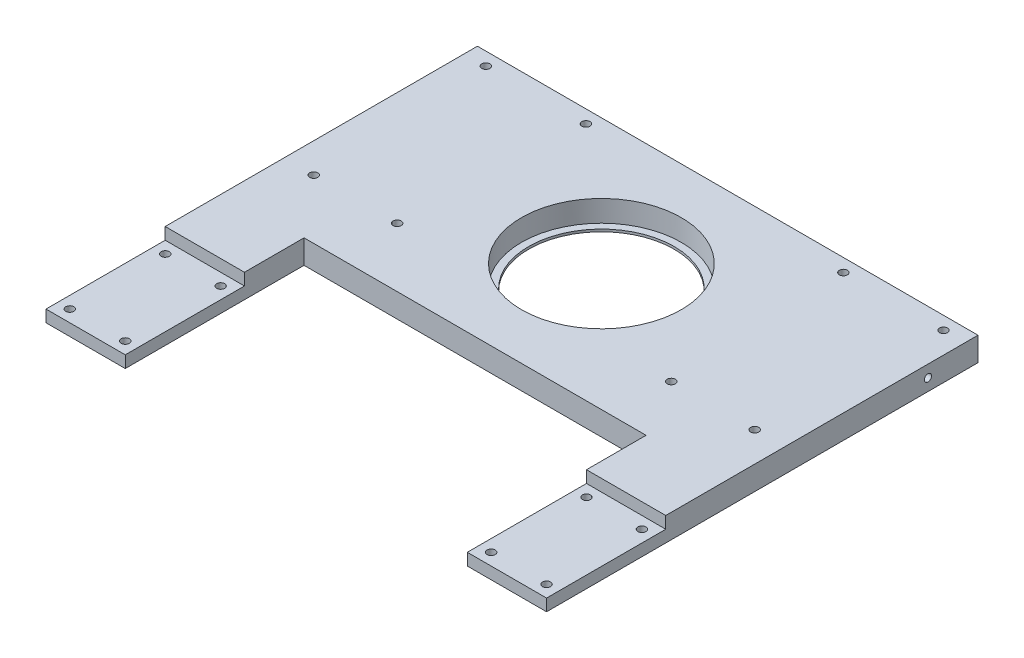
SolidWorks part; units mm, degrees
ref_plane "Ebene vorne" through (0, 0, 0) normal (0, 0, 1) x (1, 0, 0)
ref_plane "Ebene oben" through (0, 0, 0) normal (0, 1, 0) x (1, 0, 0)
ref_plane "Ebene rechts" through (0, 0, 0) normal (1, 0, 0) x (0, 0, -1)
sketch "Skizze1" plane through (0, 0, 0) normal (0, 1, 0) x (1, 0, 0)
  line L1 (-105, -210) -> (105, -210)
  line L2 (-105, -210) -> (-105, 210)
  line L3 (-105, 210) -> (105, 210)
  line L4 (105, -210) -> (105, 210)
  line L5 (-105, -210) -> (105, 210) construction
  line L6 (-105, 210) -> (105, -210) construction
  point P0 (0, 0)
  dimension "D1" = 210
  dimension "D2" = 420
extrude "Aufsatz-Linear austragen1" add sketch "Skizze1" along normal blind 10
ref_plane "Ebene1" through (0, -97.5366, 81.8429) normal (0, -0.766, 0.6428) x (1, 0, 0)
sketch "Skizze2" plane through (0, -97.5366, 81.8429) normal (0, -0.766, 0.6428) x (1, 0, 0)
  line L1 (-105, 167.2972) -> (105, 167.2972) construction
  circle A0 centre (0, 147.2972) radius 5
  dimension "D1" = 10
  dimension "D2" = 20
extrude "Schnitt-Linear austragen1" [suppressed] cut sketch "Skizze2" against normal blind 30 and the other way blind 10
sketch "Skizze3" [suppressed] plane through (0, -67.9923, 57.0523) normal (0, -0.766, 0.6428) x (1, 0, 0)
  circle A0 centre (0, 101.3345) radius 5
  dimension "D1" = 10
extrude "Aufsatz-Linear austragen2" [suppressed] add sketch "Skizze3" along normal blind 0.1
sketch "Skizze4" plane through (0, -97.5366, 81.8429) normal (0, -0.766, 0.6428) x (1, 0, 0)
  line L0 (0, 167.2972) -> (0, 159.9002) construction
  line L1 (-105, 167.2972) -> (105, 167.2972) construction
  line L2 (-25, 167.2972) -> (-25, 202.2972)
  line L3 (-25, 202.2972) -> (25, 202.2972)
  line L4 (-25, 167.2972) -> (25, 167.2972)
  line L5 (25, 167.2972) -> (25, 202.2972)
  point P10 (0, 202.2972)
  dimension "D1" = 50
  dimension "D2" = 35
extrude "Aufsatz-Linear austragen3" [suppressed] add sketch "Skizze4" against normal blind 10 separate body
sketch "Skizze5" plane through (0, 10, 0) normal (0, 1, 0) x (1, 0, 0)
  line L0 (0, 0) -> (0, -210) construction
  line L1 (-105, -210) -> (105, -210) construction
  line L2 (105, -210) -> (18, -210)
  line L3 (-18, -210) -> (-105, -56)
  line L4 (-105, 210) -> (-105, -210) construction
  line L5 (-105, -56) -> (-105, -210)
  line L6 (-105, -210) -> (-18, -210)
  line L7 (105, -56) -> (105, -210)
  line L8 (18, -210) -> (105, -56)
  line L9 (-105, 210) -> (-105, 125)
  line L10 (-105, 125) -> (105, 125)
  line L11 (105, -210) -> (105, 210) construction
  line L12 (105, 125) -> (105, 210)
  line L13 (105, 210) -> (-105, 210)
  line L14 (71.7468, -56) -> (-71.7468, -56)
  line L15 (-71.7468, -56) -> (-2.8247, -178)
  line L16 (71.7468, -56) -> (2.8247, -178)
  line L17 (-2.8247, -178) -> (2.8247, -178)
  line L18 (2.8247, -178) -> (0, -183) construction
  line L19 (-2.8247, -178) -> (0, -183) construction
  point P27 (0, -56)
  dimension "D1" = 36
  dimension "D2" = 154
  dimension "D3" = 85
  dimension "D4" = 32
  dimension "D5" = 27
extrude "Schnitt-Linear austragen2" cut sketch "Skizze5" against normal blind 10
sketch "Skizze6" plane through (0, 10, 0) normal (0, 1, 0) x (1, 0, 0)
  line L0 (0, -210) -> (0, -178) construction
  line L1 (-18, -210) -> (18, -210) construction
  line L2 (-2.8247, -178) -> (2.8247, -178) construction
  line L3 (0, -196.59) -> (-21.075, -196.59) construction
  circle A0 centre (-11, -205) radius 1.7
  circle A1 centre (-11, -188.18) radius 1.7
  circle A2 centre (11, -205) radius 1.7
  circle A3 centre (11, -188.18) radius 1.7
  dimension "D1" = 3.4
  dimension "D2" = 11
  dimension "D3" = 5
  dimension "D4" = 13.41
extrude "Schnitt-Linear austragen3" cut sketch "Skizze6" against normal through all
sketch "Skizze7" plane through (0, 0, 0) normal (0, -1, 0) x (1, 0, 0)
  line L0 (-11, 205) -> (-11, 210) construction
  line L1 (-18, 210) -> (18, 210) construction
  line L2 (-11, 205) -> (-5.1092, 205) construction
  line L3 (-11, 208.4064) -> (-8.05, 206.7032)
  line L4 (-8.05, 206.7032) -> (-8.05, 203.2968)
  line L5 (-11, 201.5936) -> (-8.05, 203.2968)
  line L6 (-11, 201.5936) -> (-13.95, 203.2968)
  line L7 (-13.95, 206.7032) -> (-13.95, 203.2968)
  line L8 (-11, 208.4064) -> (-13.95, 206.7032)
  line L9 (0, 210) -> (0, 121.6034) construction
  line L10 (11, 205) -> (11, 188.18) construction
  line L11 (11, 196.59) -> (0, 196.59) construction
  line L12 (11, 208.4064) -> (8.05, 206.7032)
  line L13 (11, 201.5936) -> (8.05, 203.2968)
  line L14 (8.05, 206.7032) -> (8.05, 203.2968)
  line L15 (11, 201.5936) -> (13.95, 203.2968)
  line L16 (13.95, 206.7032) -> (13.95, 203.2968)
  line L17 (11, 208.4064) -> (13.95, 206.7032)
  line L18 (-8.05, 186.4768) -> (-8.05, 189.8832)
  line L19 (-11, 191.5864) -> (-13.95, 189.8832)
  line L20 (-11, 191.5864) -> (-8.05, 189.8832)
  line L21 (-13.95, 186.4768) -> (-13.95, 189.8832)
  line L22 (-11, 184.7736) -> (-13.95, 186.4768)
  line L23 (-11, 184.7736) -> (-8.05, 186.4768)
  line L24 (8.05, 186.4768) -> (8.05, 189.8832)
  line L25 (11, 191.5864) -> (8.05, 189.8832)
  line L26 (11, 191.5864) -> (13.95, 189.8832)
  line L27 (13.95, 186.4768) -> (13.95, 189.8832)
  line L28 (11, 184.7736) -> (13.95, 186.4768)
  line L29 (11, 184.7736) -> (8.05, 186.4768)
  point P10 (-8.05, 205)
  dimension "D1" = 120
  dimension "D2" = 5.9
extrude "Schnitt-Linear austragen4" cut sketch "Skizze7" against normal blind 4
sketch "Skizze8" plane through (0, 10, 0) normal (0, 1, 0) x (1, 0, 0)
  line L0 (105, 115.41) -> (78.872, 115.41) construction
  line L1 (105, -56) -> (105, 125) construction
  line L2 (-105, 125) -> (105, 125) construction
  dimension "D1" = 9.59
ref_plane "Ebene2" through (0, 62.6966, -52.6087) normal (0, 0.766, -0.6428) x (-1, 0, 0)
sketch "Skizze9" plane through (0, 62.6966, -52.6087) normal (0, 0.766, -0.6428) x (-1, 0, 0)
  line L0 (-105, -81.9813) -> (-78.872, -81.9813) construction
  line L1 (-105, 49.3264) -> (-105, -89.3277) construction
  line L2 (0, -45.2589) -> (0, -16.2619) construction
  circle A0 centre (-100, -81.9813) radius 1.7
  circle A1 centre (100, -81.9813) radius 1.7
  circle A2 centre (-30, -81.9813) radius 1.7
  circle A3 centre (30, -81.9813) radius 1.7
  dimension "D1" = 3.4
  dimension "D2" = 5
  dimension "D3" = 30
extrude "Schnitt-Linear austragen5" [suppressed] cut sketch "Skizze9" against normal through all and the other way through all
ref_plane "Ebene3" through (0, 55.0361, -46.1808) normal (0, 0.766, -0.6428) x (-1, 0, 0)
sketch "Skizze10" [suppressed] plane through (0, 55.0361, -46.1808) normal (0, 0.766, -0.6428) x (-1, 0, 0)
  line L0 (-95, -81.9813) -> (-100, -81.9813) construction
  line L1 (-95, -81.9813) -> (-95, -30.0694) construction
  line L2 (-95, -78.7482) -> (-97.8, -80.3647)
  line L3 (-97.8, -80.3647) -> (-97.8, -83.5979)
  line L4 (-95, -85.2145) -> (-97.8, -83.5979)
  line L5 (-95, -85.2145) -> (-92.2, -83.5979)
  line L6 (-92.2, -80.3647) -> (-92.2, -83.5979)
  line L7 (-95, -78.7482) -> (-92.2, -80.3647)
  line L8 (0, 0) -> (0, -45.6283) construction
  line L9 (-30, -81.9813) -> (-95, -81.9813) construction
  line L10 (-62.5, -81.9813) -> (-62.5, -23.1343) construction
  line L11 (-32.8, -80.3647) -> (-32.8, -83.5979)
  line L12 (-30, -85.2145) -> (-32.8, -83.5979)
  line L13 (-30, -85.2145) -> (-27.2, -83.5979)
  line L14 (-27.2, -80.3647) -> (-27.2, -83.5979)
  line L15 (-30, -78.7482) -> (-27.2, -80.3647)
  line L16 (-30, -78.7482) -> (-32.8, -80.3647)
  line L17 (95, -78.7482) -> (92.2, -80.3647)
  line L18 (92.2, -80.3647) -> (92.2, -83.5979)
  line L19 (95, -85.2145) -> (92.2, -83.5979)
  line L20 (95, -85.2145) -> (97.8, -83.5979)
  line L21 (97.8, -80.3647) -> (97.8, -83.5979)
  line L22 (95, -78.7482) -> (97.8, -80.3647)
  line L23 (30, -78.7482) -> (32.8, -80.3647)
  line L24 (30, -78.7482) -> (27.2, -80.3647)
  line L25 (27.2, -80.3647) -> (27.2, -83.5979)
  line L26 (30, -85.2145) -> (27.2, -83.5979)
  line L27 (30, -85.2145) -> (32.8, -83.5979)
  line L28 (32.8, -80.3647) -> (32.8, -83.5979)
  point P9 (-97.8, -81.9813)
  point P31 (97.8, -81.9813)
  dimension "D1" = 120
  dimension "D2" = 5.6
extrude "Schnitt-Linear austragen6" [suppressed] cut sketch "Skizze10" against normal blind 10 and the other way blind 5
sketch "Skizze13" plane through (0, 10, 0) normal (0, 1, 0) x (1, 0, 0)
  line L0 (71.7468, -56) -> (105, -56) construction
  line L1 (71.7468, -56) -> (96.9548, -70.2409) construction
  line L2 (105, -56) -> (18, -210) construction
  line L3 (0, 0) -> (0, -38.1435) construction
  line L4 (2.8247, -178) -> (71.7468, -56) construction
  line L5 (84.3508, -63.1205) -> (108.762, -19.9098) construction
  line L6 (105, -56) -> (105, 125) construction
  line L7 (88.3734, -56) -> (88.3734, -1) construction
  line L8 (99, -58.9512) -> (105.7595, -46.9862) construction
  line L9 (87.7845, -86.4734) -> (62.5765, -72.2325) construction
  line L10 (77.1638, -80.4734) -> (91.1741, -80.4734) construction
  circle A0 centre (99, -58.9512) radius 1.7
  circle A1 centre (76.9708, -58.9512) radius 1.7
  circle A2 centre (86.8414, -80.4734) radius 1.7
  circle A3 centre (-86.8414, -80.4734) radius 1.7
  circle A4 centre (-99, -58.9512) radius 1.7
  circle A5 centre (-76.9708, -58.9512) radius 1.7
  dimension "D1" = 6
  dimension "D5" = 35
  dimension "D3" = 3.4
  dimension "D6" = 3.4
  dimension "D2" = 6
  dimension "D4" = 6
extrude "Schnitt-Linear austragen7" [suppressed] cut sketch "Skizze13" against normal through all
sketch "Skizze14" plane through (103.579, 0, 58.5154) normal (0.8707, 0, 0.4919) x (0.4919, 0, -0.8707)
  line L0 (-32.111, 5) -> (-32.111, 10)
  line L5 (2.889, 0) -> (2.889, 10) construction
  line L6 (-32.111, 5) -> (2.889, 5)
  line L7 (2.889, 10) -> (-173.9866, 10) construction
  line L8 (-32.111, 10) -> (2.889, 10)
  line L9 (2.889, 10) -> (2.889, 5)
  dimension "D1" = 35
extrude "Schnitt-Linear austragen8" [suppressed] cut sketch "Skizze14" against normal up to surface (28.9525 mm away)
mirror "Spiegeln1" [suppressed] about plane through (0, 0, 0) normal (1, 0, 0)
sketch "Skizze15" [suppressed] plane through (95, 0, 0) normal (1, 0, 0) x (0, 0, -1)
  line L0 (4, 10) -> (4, 0)
  line L1 (4, 0) -> (65, 0)
  line L2 (65, 0) -> (65, 10)
  line L3 (65, 10) -> (4, 10)
extrude "Schnitt-Linear austragen9" [suppressed] cut sketch "Skizze15" against normal through all
sketch "Skizze16" plane through (0, 0, 0) normal (0, -1, 0) x (1, 0, 0)
  line L0 (0, 210) -> (0, 178) construction
  line L1 (-18, 210) -> (18, 210) construction
  line L2 (-2.8247, 178) -> (2.8247, 178) construction
  line L3 (11, 196.59) -> (0, 196.59) construction
  line L4 (11, 205) -> (11, 188.18) construction
  line L6 (-17.5, 193.09) -> (17.5, 193.09)
  line L7 (-17.5, 193.09) -> (-17.5, 200.09)
  line L8 (-17.5, 200.09) -> (17.5, 200.09)
  line L9 (17.5, 193.09) -> (17.5, 200.09)
  line L10 (-17.5, 193.09) -> (17.5, 200.09) construction
  line L11 (-17.5, 200.09) -> (17.5, 193.09) construction
  dimension "D1" = 7
  dimension "D2" = 35
extrude "Schnitt-Linear austragen10" cut sketch "Skizze16" against normal blind 5
sketch "Skizze17" plane through (17.5, 0, 0) normal (-1, 0, 0) x (0, 0, 1)
  line L0 (196.59, 0) -> (196.59, 11.1261) construction
  line L1 (193.09, 0) -> (200.09, 0) construction
  line L2 (193.09, 5) -> (196.59, 8.5)
  line L3 (196.59, 8.5) -> (200.09, 5)
  line L4 (200.09, 5) -> (193.09, 5)
  dimension "D1" = 90
extrude "Schnitt-Linear austragen11" cut sketch "Skizze17" along normal up to surface (35 mm away) up to face at (-17.5, 2.5, 196.59)
sketch "Skizze18" [suppressed] plane through (0, 10, 0) normal (0, 1, 0) x (1, 0, 0)
  line L0 (0, -210) -> (0, 0) construction
  line L1 (-18, -210) -> (18, -210) construction
  line L2 (62.5765, -72.2325) -> (35.4483, -67.5372)
  line L3 (15.3378, -155.8503) -> (-22.1774, -134.6566)
  line L4 (2.8247, -178) -> (62.5765, -72.2325) construction
  line L5 (-15.3378, -155.8503) -> (22.1774, -134.6566)
  line L6 (58.6594, -79.166) -> (40.7308, -76.063)
  line L7 (0, -147.1854) -> (19.5429, -147.1854) construction
  line L8 (0, -95.4) -> (31.4297, -95.4) construction
  line L9 (11.6488, -162.3803) -> (0, -155.7995)
  line L10 (-71.7468, -56) -> (-2.8247, -178) construction
  line L11 (0, -95.4) -> (-37.5153, -116.5937) construction
  line L12 (-37.5153, -116.5937) -> (-39.2566, -117.5774) construction
  line L13 (-11.6488, -162.3803) -> (0, -155.7995)
  line L14 (-58.6594, -79.166) -> (-40.7308, -76.063)
  line L15 (-62.5765, -72.2325) -> (-35.4483, -67.5372)
  circle A0 centre (0, -95.4) radius 33.5
  arc A1 (7.4594, -151.3994) -> (7.4594, -142.9713) centre (9.84, -147.1854) cw
  arc A2 (-7.4594, -151.3994) -> (-7.4594, -142.9713) centre (-9.84, -147.1854) ccw
  circle A3 centre (0, -95.4) radius 45.0879
  point P17 (0, -147.1854)
  point P36 (5, -147.1854)
  point P40 (-5, -147.1854)
  line M16 (62.5765, -72.2325) -> (2.8247, -178)
  line M18 (-2.8247, -178) -> (-71.7468, -56)
  dimension "D2" = 67
  dimension "D5" = 2
  dimension "D4" = 10
  dimension "D1" = 114.6
  dimension "D3" = 7.5
  dimension "D6" = 7.5
extrude "Aufsatz-Linear austragen4" [suppressed] add sketch "Skizze18" against normal blind 10 contours A3 L15 L14 M18 | A3 A0 M16 M18 | A3 L6 L2 M16 | A2 L5 L3 | A3 L3 L5 | L3 A1 L5 | L13 L9 L3 L5 M18 M16
sketch "Skizze19" [suppressed] plane through (0, 0, 0) normal (0, -1, 0) x (1, 0, 0)
  circle A0 centre (0, 35.4) radius 31.5
  circle A1 centre (0, 35.4) radius 33.5
  circle A2 centre (0, 35.4) radius 33.5 construction
  dimension "D1" = 63
extrude "Aufsatz-Linear austragen5" [suppressed] add sketch "Skizze19" against normal blind 1
sketch "Skizze20" plane through (0, 10, 0) normal (0, 1, 0) x (1, 0, 0)
  line L0 (105, 119.52) -> (55.4083, 119.52) construction
  line L1 (105, -56) -> (105, 125) construction
  line L2 (-105, 125) -> (105, 125) construction
  line L3 (0, 125) -> (0, 96.9732) construction
  line L4 (105, 43.82) -> (35.5869, 43.82) construction
  circle A0 centre (96, 119.52) radius 1.7
  circle A1 centre (54, 119.52) radius 1.7
  circle A2 centre (-54, 119.52) radius 1.7
  circle A3 centre (-96, 119.52) radius 1.7
  circle A4 centre (92.5, 43.82) radius 1.7
  circle A5 centre (57.5, 43.82) radius 1.7
  circle A6 centre (-92.5, 43.82) radius 1.7
  circle A7 centre (-57.5, 43.82) radius 1.7
  dimension "D1" = 3.4
  dimension "D2" = 5.48
  dimension "D3" = 9
  dimension "D4" = 42
  dimension "D5" = 75.7
  dimension "D6" = 12.5
  dimension "D7" = 35
extrude "Schnitt-Linear austragen12" cut sketch "Skizze20" against normal through all
sketch "Skizze21" plane through (0, 10, 0) normal (0, 1, 0) x (1, 0, 0)
  line L0 (-71.7468, -56) -> (-71.7468, 19)
  line L1 (-71.7468, 19) -> (71.7468, 19)
  line L2 (71.7468, 19) -> (71.7468, -56)
  line L3 (71.7468, -56) -> (-71.7468, -56) construction
  line L4 (-71.7468, -56) -> (71.7468, -56)
  dimension "D1" = 75
extrude "Schnitt-Linear austragen13" cut sketch "Skizze21" against normal through all
sketch "Skizze22" plane through (0, 10, 0) normal (0, 1, 0) x (1, 0, 0)
  line L0 (-71.7468, -56) -> (-2.8247, -178)
  arc A0 (-71.7468, -56) -> (-2.8247, -178) centre (55.7113, -64.4627) ccw
  line M19 (-2.8247, -178) -> (-71.7468, -56)
extrude "Schnitt-Linear austragen14" cut sketch "Skizze22" against normal through all contours M19 region at (-44.6278, 10, 121.1478)
sketch "Skizze23" plane through (0, 10, 0) normal (0, 1, 0) x (1, 0, 0)
  line L0 (-18, -210) -> (-105, -56) construction
  line L1 (-105, -56) -> (-18, -210)
  arc A0 (-18, -210) -> (-105, -56) centre (108.9155, -36.7263) cw
  arc A2 (-71.7468, -56) -> (-2.8247, -178) centre (55.7113, -64.4627) ccw construction
  dimension "D1" = 60
extrude "Aufsatz-Linear austragen6" add sketch "Skizze23" against normal blind 10
mirror "Spiegeln2" about plane through (0, 0, 0) normal (1, 0, 0) of "Aufsatz-Linear austragen6", "Schnitt-Linear austragen14"
sketch "Skizze25" plane through (0, 10, 0) normal (0, 1, 0) x (1, 0, 0)
  line L0 (-105, -56) -> (-71.7468, -56) construction
  line L1 (-105, -6) -> (-105, -56) construction
  line L2 (-105, -6) -> (-71.7468, -6) construction
  line L3 (-71.7468, 19) -> (-71.7468, -56) construction
  line L4 (-88.3734, -6) -> (-88.3734, -56) construction
  line L5 (-105, -31) -> (-71.7468, -31) construction
  line L6 (-105, 125) -> (-105, -56) construction
  circle A0 centre (-100, -11) radius 1.7
  circle A1 centre (-76.7468, -11) radius 1.7
  circle A2 centre (-76.7468, -51) radius 1.7
  circle A3 centre (-100, -51) radius 1.7
  dimension "D2" = 3.4
  dimension "D1" = 50
  dimension "D3" = 5
  dimension "D4" = 5
extrude "Schnitt-Linear austragen15" cut sketch "Skizze25" against normal through all
sketch "Skizze26" plane through (-105, 0, 0) normal (-1, 0, 0) x (0, 0, 1)
  line L0 (6, 5) -> (6, 13.1015)
  line L1 (56, 0) -> (56, 10) construction
  line L2 (56, 5) -> (6, 5)
  line L4 (-125, 0) -> (56, 0) construction
  line L5 (56, 5) -> (56, 0)
  line L6 (6, 13.1015) -> (200.6846, 82.5463)
  line L7 (200.6846, 82.5463) -> (242.9972, -41.0376)
  line L8 (242.9972, -41.0376) -> (91.2415, -60.2848)
  line L9 (91.2415, -60.2848) -> (56, 0)
  dimension "D1" = 50
mirror "Spiegeln3" about plane through (0, 0, 0) normal (1, 0, 0) of "Schnitt-Linear austragen15"
extrude "Schnitt-Linear austragen16" cut sketch "Skizze26" against normal through all
sketch "Skizze27" plane through (0, 10, 0) normal (0, 1, 0) x (1, 0, 0)
  line L0 (0, 19) -> (0, 125) construction
  line L1 (71.7468, 19) -> (-71.7468, 19) construction
  line L2 (-105, 125) -> (105, 125) construction
  circle A0 centre (0, 72) radius 33.5
  dimension "D1" = 67
extrude "Schnitt-Linear austragen17" cut sketch "Skizze27" against normal through all
sketch "Skizze28" plane through (0, 0, 0) normal (0, -1, 0) x (1, 0, 0)
  circle A0 centre (0, -72) radius 30.5
  circle A1 centre (0, -72) radius 33.5 construction
  circle A2 centre (0, -72) radius 36.0063
  dimension "D1" = 3
extrude "Aufsatz-Linear austragen7" add sketch "Skizze28" against normal blind 1
sketch "Skizze29" plane through (-105, 0, 0) normal (-1, 0, 0) x (0, 0, 1)
  line L0 (-125, 5) -> (-93.4233, 5) construction
  line L1 (-125, 0) -> (-125, 10) construction
  circle A0 centre (-104, 5) radius 1.5
  dimension "D1" = 3
  dimension "D2" = 21
extrude "Schnitt-Linear austragen18" cut sketch "Skizze29" against normal blind 10
sketch "Skizze30" plane through (0, 0, -125) normal (0, 0, -1) x (-1, 0, 0)
  line L0 (105, 5) -> (60.2539, 5) construction
  line L1 (105, 0) -> (105, 10) construction
  circle A0 centre (100, 5) radius 1.5
  circle A1 centre (84, 5) radius 1.5
  dimension "D1" = 3
  dimension "D2" = 5
  dimension "D3" = 21
extrude "Schnitt-Linear austragen19" cut sketch "Skizze30" against normal blind 10
mirror "Spiegeln4" about plane through (0, 0, 0) normal (1, 0, 0) of "Schnitt-Linear austragen18", "Schnitt-Linear austragen19"
sketch "Skizze31" plane through (0, 0, 0) normal (0, -1, 0) x (1, 0, 0)
  line L0 (0, -125) -> (0, -73.0202) construction
  line L1 (-105, -125) -> (105, -125) construction
  circle A0 centre (-96, -119.52) radius 2.95
  circle A1 centre (-54, -119.52) radius 2.95
  circle A2 centre (-92.5, -43.82) radius 2.95
  circle A3 centre (-57.5, -43.82) radius 2.95
  circle A4 centre (57.5, -43.82) radius 2.95
  circle A5 centre (92.5, -43.82) radius 2.95
  circle A6 centre (54, -119.52) radius 2.95
  circle A7 centre (96, -119.52) radius 2.95
  dimension "D1" = 5.9
extrude "Schnitt-Linear austragen20" cut sketch "Skizze31" against normal blind 3.5
